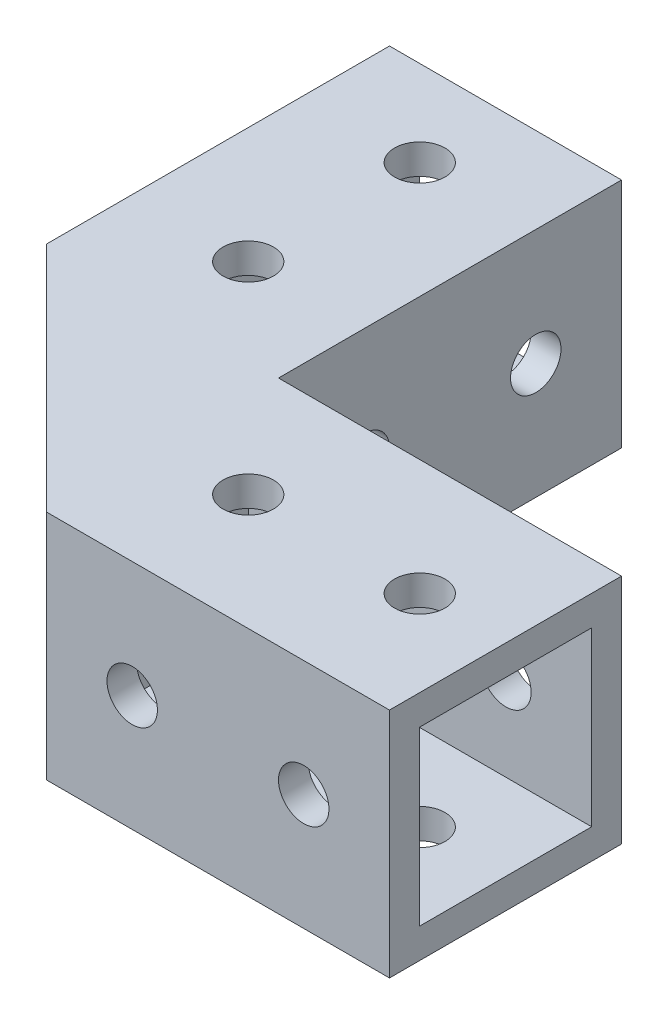
SolidWorks part; units mm, degrees
ref_plane "Front Plane" through (0, 0, 0) normal (0, 0, 1) x (1, 0, 0)
ref_plane "Top Plane" through (0, 0, 0) normal (0, 1, 0) x (1, 0, 0)
ref_plane "Right Plane" through (0, 0, 0) normal (1, 0, 0) x (0, 0, -1)
other "Configuration Table"
sketch "sketch1" plane through (0, 0, 0) normal (0, 1, 0) x (1, 0, 0)
  line L0 (0, -11.5) -> (8.5, -11.5) construction
  line L1 (0, 0) -> (34, 0)
  line L2 (0, 0) -> (0, -23)
  line L3 (0, -23) -> (34, -23)
  line L4 (34, 0) -> (34, -23)
  line L5 (8.5, -11.5) -> (25.5, -11.5) construction
  circle A1 centre (8.5, -11.5) radius 2.5
  circle A2 centre (25.5, -11.5) radius 2.5
  dimension "D4" = 5
  dimension "D1" = 23
  dimension "D2" = 34
  dimension "D3" = 8.5
  dimension "D6" = 17
extrude "Boss-Extrude1" add sketch "sketch1" along normal blind 23
sketch "Sketch6" plane through (0, 0, 0) normal (0, 0, -1) x (-1, 0, 0)
  line L0 (-34, 11.5) -> (-25.5, 11.5) construction
  line L1 (-25.5, 11.5) -> (-8.5, 11.5) construction
  line L4 (-34, 0) -> (0, 0)
  line L5 (0, 0) -> (0, 23)
  line L6 (0, 23) -> (-34, 23)
  line L7 (-34, 23) -> (-34, 0)
  line L8 (-34, 0) -> (0, 0)
  line L9 (0, 0) -> (0, 23)
  line L10 (0, 23) -> (-34, 23)
  line L11 (-34, 23) -> (-34, 0)
  circle A0 centre (-25.5, 11.5) radius 2.5
  circle A1 centre (-8.5, 11.5) radius 2.5
  dimension "D3" = 5
  dimension "D2" = 8.5
  dimension "D5" = 17
extrude "Cut-Extrude10" cut sketch "Sketch6" against normal through all flip side to cut
sketch "Sketch7" plane through (34, 0, 0) normal (1, 0, 0) x (0, 0, -1)
  line L0 (-23, 11.5) -> (0, 11.5) construction
  line L4 (-23, 0) -> (0, 0)
  line L5 (0, 0) -> (0, 23)
  line L6 (0, 23) -> (-23, 23)
  line L7 (-23, 23) -> (-23, 0)
  line L8 (-23, 0) -> (0, 0)
  line L9 (0, 0) -> (0, 23)
  line L10 (0, 23) -> (-23, 23)
  line L11 (-23, 23) -> (-23, 0)
  line L14 (-20.04, 20.04) -> (-2.96, 20.04)
  line L15 (-20.04, 20.04) -> (-20.04, 2.96)
  line L16 (-20.04, 2.96) -> (-2.96, 2.96)
  line L17 (-2.96, 20.04) -> (-2.96, 2.96)
  line L18 (-20.04, 20.04) -> (-2.96, 2.96) construction
  line L19 (-20.04, 2.96) -> (-2.96, 20.04) construction
  point P6 (-11.5, 11.5)
  dimension "D2" = 17.08
extrude "Cut-Extrude11" cut sketch "Sketch7" against normal blind 34 flip side to cut
sketch "Sketch9" plane through (0, 0, 0) normal (0, 1, 0) x (1, 0, 0)
  line L0 (0, 0) -> (34, 0) construction
  line L1 (0, 0) -> (24.0416, 24.0416) construction
  dimension "D1" = 45
ref_plane "Plane2" through (0, 0, 0) normal (-0.7071, 0, -0.7071) x (-0.7071, 0, 0.7071)
mirror "Mirror6" about plane through (0, 0, 0) normal (-0.7071, 0, -0.7071) of bodies 118 110
sketch "Sketch11" plane through (0, 0, 0) normal (0, 1, 0) x (1, 0, 0)
  line L0 (-23, 0) -> (0, -23)
  line L1 (0, 0) -> (-23, 0) construction
  line L2 (0, 0) -> (0, -23) construction
  line L3 (0, 0) -> (-23, 0)
  line L4 (0, 0) -> (0, -23)
extrude "Boss-Extrude2" add sketch "Sketch11" along normal blind 23
sketch "Sketch13" plane through (0, 0, 0) normal (0, 1, 0) x (1, 0, 0)
  line L0 (-11.5, 8.5) -> (5.1708, 5.1708) construction
  line L1 (0, 0) -> (24.0416, 24.0416) construction
  line L2 (5.1708, 5.1708) -> (8.5, -11.5) construction
  line L4 (8.7064, 8.7064) -> (0, 17)
  line L5 (0, 34) -> (0, 0) construction
  line L6 (8.7064, 8.7064) -> (17, 0)
  line L7 (0, 0) -> (34, 0) construction
  line L8 (0, 0) -> (24.0416, 24.0416) construction
  line L9 (0, 17) -> (0, 0)
  line L10 (0, 0) -> (17, 0)
  circle A0 centre (8.5, -11.5) radius 2.5 construction
  circle A1 centre (-11.5, 8.5) radius 2.5 construction
  circle A2 centre (8.5, -11.5) radius 2.5 construction
  circle A3 centre (-11.5, 8.5) radius 2.5 construction
  circle A4 centre (5.1708, 5.1708) radius 2.5
  dimension "D3" = 5
  dimension "D2" = 5
  dimension "D1" = 17
  dimension "D4" = 17
extrude "Boss-Extrude3" add sketch "Sketch13" along normal blind 4
equation "\"D2@sketch1\" = \"length\""
equation "\"holes\"= 2'Holes per side"
equation "\"cdist\"= 17mm'centre distance between holes"
equation "\"width\"= \"insetwidth\" + 2 * \"shellwidth\""
equation "\"length\"= \"cdist\" * \"holes\""
equation "\"D1@sketch1\"=\"width\""
equation "\"hdiam\"= 5mm'Hole diametre"
equation "\"D4@sketch1\" = \"hdiam\""
equation "\"D6@sketch1\" = \"cdist\""
equation "\"D5@sketch1\" = \"holes\""
equation "\"D2@Sketch6\"=\"cdist\"/2"
equation "\"D3@Sketch6\"=\"hdiam\""
equation "\"D5@Sketch6\"=\"cdist\""
equation "\"D4@Sketch6\"=\"holes\""
equation "\"D1@Boss-Extrude1\"=\"width\""
equation "\"joint\"= 90"
equation "\"D1@Sketch9\"=\"joint\"/2"
equation "\"D1@Boss-Extrude2\"=\"width\""
equation "\"D2@Sketch13\"=\"hdiam\""
equation "\"D4@Sketch13\"=\"cdist\""
equation "\"D1@Boss-Extrude3\"=\"supportheight\""
equation "\"supportheight\"= 4mm"
equation "\"tolerance\"= 0.04mm"
equation "\"insetwidth\"= 17mm"
equation "\"D1@Cut-Extrude11\"=\"length\""
equation "\"true\"= 1"
equation "\"false\"= 0"
equation "\"supportenabled\"= \"true\""
equation "\"Boss-Extrude3\"= IIF ( \"supportenabled\" < \"true\" , \"suppressed\" , \"unsuppressed\" )"
equation "\"D2@Sketch7\"=\"insetwidth\"+\"tolerance\"*2"
equation "\"shellwidth\"= 3mm"
